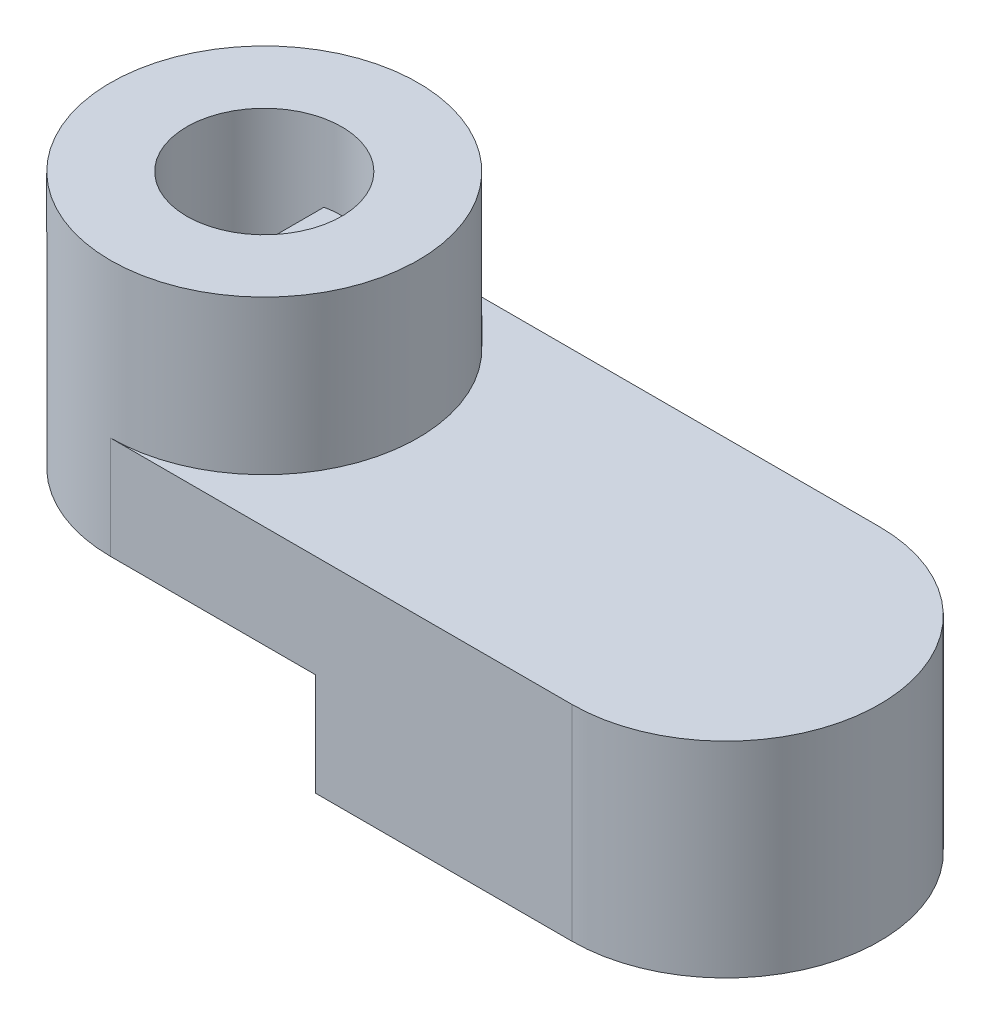
SolidWorks part; units mm, degrees
ref_plane "Front" through (0, 0, 0) normal (0, 0, 1) x (1, 0, 0)
ref_plane "Top" through (0, 0, 0) normal (0, 1, 0) x (1, 0, 0)
ref_plane "Right" through (0, 0, 0) normal (1, 0, 0) x (0, 0, -1)
sketch "Sketch1" plane through (0, 0, 0) normal (0, 0, 1) x (1, 0, 0)
  line L8 (0, 0) -> (-12.7, 0)
  line L11 (-23.8125, 3.175) -> (-23.8125, 6.35)
  line L12 (-23.8125, 6.35) -> (0, 6.35)
  line L15 (0, 6.35) -> (0, 0)
  line L16 (-12.7, 0) -> (-12.7, 3.175)
  line L17 (-12.7, 3.175) -> (-23.8125, 3.175)
  dimension "D1" = 3.175
  dimension "D2" = 23.8125
  dimension "D3" = 12.7
extrude "Boss-Extrude1" add sketch "Sketch1" along normal mid plane 9.525
sketch "Sketch3" plane through (0, 0, 0) normal (0, -1, 0) x (1, 0, 0)
  line L0 (-12.7, 4.7625) -> (0, 4.7625) construction
  line L1 (-23.8125, 4.7625) -> (-23.8125, -4.7625) construction
  line L2 (-23.8125, 0) -> (-23.8125, 4.7625)
  line L3 (-23.8125, 4.7625) -> (-19.05, 4.7625)
  line L4 (-19.05, -4.7625) -> (-23.8125, -4.7625)
  line L5 (-23.8125, -4.7625) -> (-23.8125, 0)
  line L6 (0, 4.7625) -> (0, -4.7625) construction
  line L7 (-12.7, 4.7625) -> (0, 4.7625) construction
  line L8 (-12.7, -4.7625) -> (0, -4.7625) construction
  line L9 (-4.7625, 4.7625) -> (0, 4.7625)
  line L10 (0, 4.7625) -> (0, 0)
  line L11 (0, 0) -> (0, -4.7625)
  line L12 (0, -4.7625) -> (-4.7625, -4.7625)
  arc A0 (-19.05, 4.7625) -> (-19.05, -4.7625) centre (-19.05, 0) ccw
  arc A1 (-4.7625, -4.7625) -> (-4.7625, 4.7625) centre (-4.7625, 0) ccw
  line M2 (-12.7, -4.7625) -> (0, -4.7625)
  line M3 (0, -4.7625) -> (0, 4.7625)
  line M4 (0, 4.7625) -> (-12.7, 4.7625)
extrude "Cut-Extrude2" cut sketch "Sketch3" against normal up to next contours A0 M4 | A0 M2 | A1 M3 M4 | A1 M2 M3 region at (-22.7487, 0, -3.6987) region at (-22.7487, 0, 3.6987) region at (-1.0638, 0, -3.6987) region at (-1.0638, 0, 3.6987)
sketch "Sketch5" plane through (0, 6.35, 0) normal (0, 1, 0) x (1, 0, 0)
  circle A0 centre (-19.05, 0) radius 4.7625
  arc A1 (-19.05, 4.7625) -> (-19.05, -4.7625) centre (-19.05, 0) ccw construction
  circle A2 centre (-19.05, 0) radius 2.4
  dimension "D1" = 4.8
extrude "Boss-Extrude2" add sketch "Sketch5" along normal blind 4.7625
sketch "Sketch6" plane through (0, 6.35, 0) normal (0, 1, 0) x (1, 0, 0)
  line L0 (-19.55, -2.3473) -> (-19.55, 2.3473)
  line L5 (-18.55, -2.3473) -> (-18.55, 2.3473)
  line L6 (-18.55, 0) -> (-19.55, 0) construction
  circle A1 centre (-19.05, 0) radius 2.4 construction
  arc A2 (-18.55, 2.3473) -> (-19.55, 2.3473) centre (-19.05, 0) ccw
  arc A3 (-19.55, -2.3473) -> (-18.55, -2.3473) centre (-19.05, 0) ccw
  dimension "D1" = 1
extrude "Boss-Extrude3" add sketch "Sketch6" along normal blind 2.3813
